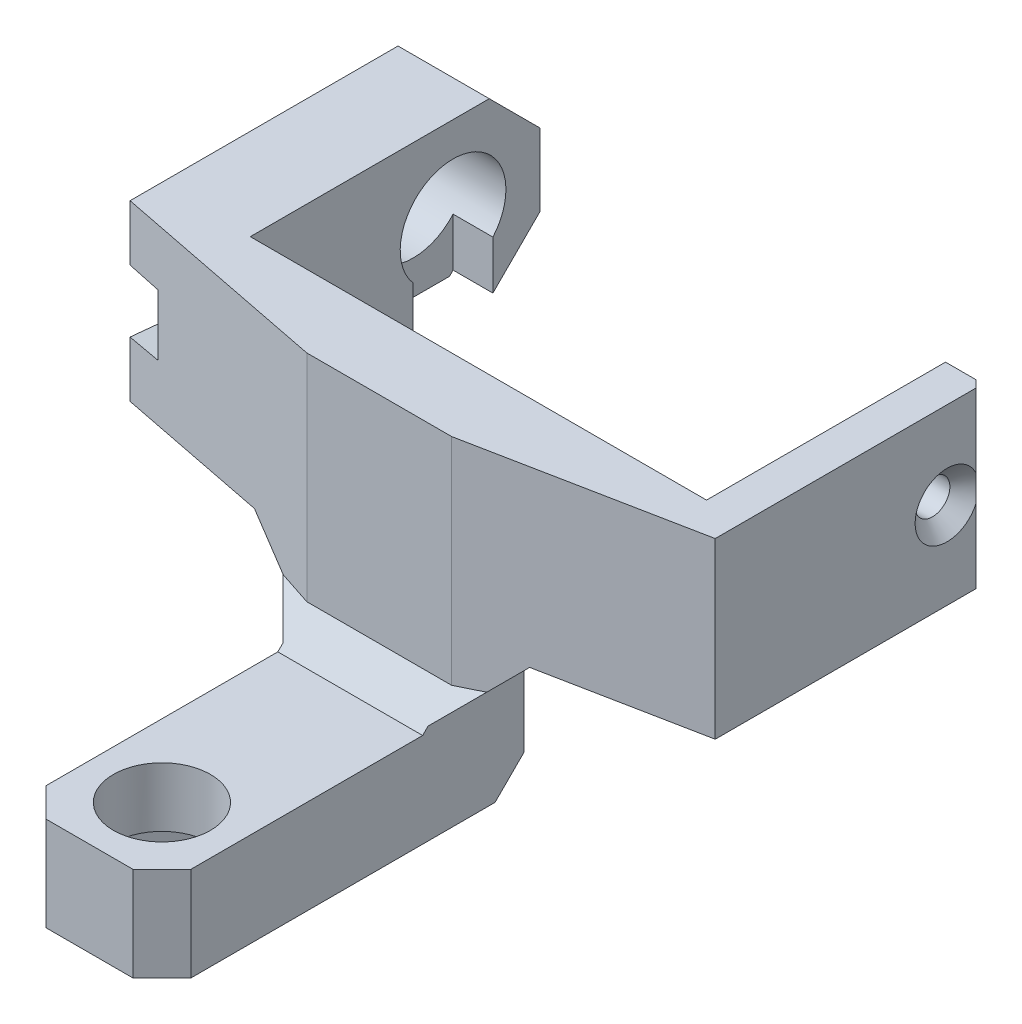
SolidWorks part; units mm, degrees
ref_plane "Front" through (0, 0, 0) normal (0, 0, 1) x (1, 0, 0)
ref_plane "Top" through (0, 0, 0) normal (0, 1, 0) x (1, 0, 0)
ref_plane "Right" through (0, 0, 0) normal (1, 0, 0) x (0, 0, -1)
sketch "Sketch1" plane through (0, 0, 0) normal (0, 0, 1) x (1, 0, 0)
  line L5 (20.2, -6) -> (-20.2, -6)
  line L6 (20.2, -6) -> (20.2, 6)
  line L7 (20.2, 6) -> (-20.2, 6)
  line L8 (-20.2, -6) -> (-20.2, 6)
  line L9 (20.2, -6) -> (-20.2, 6) construction
  line L10 (20.2, 6) -> (-20.2, -6) construction
  point P0 (0, 0)
  dimension "D1" = 40.4
  dimension "D2" = 12
extrude "Boss-Extrude1" add sketch "Sketch1" along normal blind 22 contours L7 L8 L5 L6
sketch "Sketch2" plane through (0, 6, 0) normal (0, 1, 0) x (1, 0, 0)
  line L0 (20.2, 0) -> (-20.2, 0) construction
  line L1 (-13.9, 0) -> (17.6, 0)
  line L2 (-13.9, 0) -> (-13.9, -20)
  line L3 (-13.9, -20) -> (17.6, -20)
  line L4 (17.6, 0) -> (17.6, -20)
  line L5 (-20.2, -22) -> (-20.2, 0) construction
  line L6 (20.2, -22) -> (20.2, 0) construction
  dimension "D1" = 6.3
  dimension "D2" = 31.5
  dimension "D3" = 20
  dimension "D4" = 2.6
extrude "Cut-Extrude1" cut sketch "Sketch2" against normal up to next
sketch "Sketch4" plane through (20.2, 0, 0) normal (1, 0, 0) x (0, 0, -1)
  line L0 (0, -6) -> (0, 6) construction
  circle A0 centre (-6, 0) radius 0.9
  dimension "D1" = 1.8
  dimension "D2" = 6
extrude "Cut-Extrude2" cut sketch "Sketch4" against normal up to next
ref_plane "Plane1" through (0, -36, 0) normal (0, -1, 0) x (-1, 0, 0)
sketch "Sketch14" plane through (0, 0, 22) normal (0, 0, 1) x (1, 0, 0)
  line L4 (20.2, -6) -> (20.2, 6)
  line L5 (20.2, 6) -> (-20.2, 6)
  line L6 (-20.2, 6) -> (-20.2, -6)
  line L7 (-20.2, -6) -> (20.2, -6)
  line L8 (20.2, -6) -> (20.2, 6)
  line L9 (20.2, 6) -> (-20.2, 6)
  line L10 (-20.2, 6) -> (-20.2, -6)
  line L11 (-20.2, -6) -> (20.2, -6)
  dimension "D1" = 0
chamfer "Chamfer1" distance 3.5 angle 45 4 edges at (-17.05, -6, 0) (-17.05, 6, 0) (18.9, -6, 0) (18.9, 6, 0)
hole_wizard "CSK for M2 Flat Head Machine Screw1" positions "Sketch17" profile "Sketch18" countersink size "M2" standard "ANSI Metric"
sketch "Sketch17" plane through (20.2, 0, 0) normal (1, 0, 0) x (0, 0, -1)
  point P0 (-6, 0)
sketch "Sketch18" plane through (20.2, 0, 6) normal (0, 1, 0) x (0, 0, -1)
  line L0 (0, 0) -> (0, 13.421)
  line L1 (0, 13.421) -> (1.2, 12.7)
  line L2 (1.2, 12.7) -> (1.2, 1)
  line L3 (1.2, 1) -> (2.2, 0)
  line L5 (2.2, 0) -> (0, 0)
  line L6 (-1.2, 1) -> (-2.2, 0) construction
  line L10 (0, 13.421) -> (-1.2, 12.7) construction
  line L11 (0, -6.35) -> (0, 107.95) construction
  dimension "Hole Dia." = 2.4
  dimension "Hole Depth" = 12.7
  dimension "Near C'Sink Dia." = 4.4
  dimension "Near C'Sink Angle" = 90
  dimension "Drill Angle" = 118
chamfer "Chamfer2" distance 4 angle 45 1 edges at (20.2, 0, 0)
ref_plane "Plane10" through (0, 0, 0) normal (0, -1, 0) x (-1, 0, 0)
sketch "Sketch20" plane through (17.6, 0, 0) normal (-1, 0, 0) x (0, 0, 1)
  circle A0 centre (6, 0) radius 2.5
  circle A1 centre (6, 0) radius 1.2
  dimension "D1" = 5
extrude "Boss-Extrude2" add sketch "Sketch20" along normal blind 0.5
sketch "Sketch25" plane through (0, -6, 0) normal (0, -1, 0) x (1, 0, 0)
  line L0 (0, 0) -> (0, 22) construction
  line L1 (20.2, 22) -> (-20.2, 22) construction
  line L2 (20.2, 22) -> (-20.2, 22)
  line L3 (-20.2, 22) -> (-5, 25)
  line L4 (-5, 25) -> (5, 25)
  line L5 (-13.9, 20) -> (17.6, 20) construction
  line L6 (20.2, 22) -> (5, 25)
  point P14 (0, 25)
  dimension "D1" = 5
  dimension "D2" = 5
extrude "Boss-Extrude3" add sketch "Sketch25" against normal through all
sketch "Sketch5" plane through (-20.2, 0, 0) normal (-1, 0, 0) x (0, 0, 1)
  line L0 (6, 0) -> (22.45, 0) construction
  line L1 (6.3157, 3.3351) -> (22.6196, 1.792) construction
  line L2 (6.3157, -3.3351) -> (22.6196, -1.792) construction
  line L3 (0, -2.5) -> (0, 2.5) construction
  line L4 (6.3439, 3.6338) -> (22.6479, 2.0907)
  line L5 (6.3439, -3.6338) -> (22.6479, -2.0907)
  circle A0 centre (6, 0) radius 3.35 construction
  circle A1 centre (22.45, 0) radius 1.8 construction
  arc A2 (6.3157, 3.3351) -> (6.3157, -3.3351) centre (6, 0) ccw construction
  arc A3 (22.6196, 1.792) -> (22.6196, -1.792) centre (22.45, 0) cw construction
  arc A4 (22.6479, 2.0907) -> (22.6479, -2.0907) centre (22.45, 0) cw
  arc A5 (6.3439, 3.6338) -> (6.3439, -3.6338) centre (6, 0) ccw
  point P6 (2.65, 0)
  point P7 (24.25, 0)
  point P13 (0, 0)
  dimension "D1" = 6.7
  dimension "D2" = 3.6
  dimension "D4" = 0.3
  dimension "D3" = 21.6
  dimension "D5" = 6
extrude "Cut-Extrude3" cut sketch "Sketch5" against normal blind 2.4
sketch "Sketch23" plane through (-17.8, 0, 0) normal (-1, 0, 0) x (0, 0, 1)
  circle A0 centre (6, 0) radius 3.65
  arc A1 (6.3439, 3.6338) -> (6.3439, -3.6338) centre (6, 0) ccw construction
extrude "Cut-Extrude4" cut sketch "Sketch23" against normal blind 22.4
sketch "Sketch24" plane through (0, 0, 0) normal (0, -1, 0) x (-1, 0, 0)
  line L0 (13.9, -2.35) -> (13.9, -9.65) construction
  line L1 (16.65, -8.75) -> (11.15, -8.75)
  line L2 (16.65, -8.75) -> (16.65, -3.25)
  line L3 (16.65, -3.25) -> (11.15, -3.25)
  line L4 (11.15, -8.75) -> (11.15, -3.25)
  line L5 (16.65, -8.75) -> (11.15, -3.25) construction
  line L6 (16.65, -3.25) -> (11.15, -8.75) construction
  point P0 (13.9, -6)
  dimension "D1" = 5.5
extrude "Cut-Extrude5" cut sketch "Sketch24" along normal blind 22.4
sketch "Sketch26" plane through (0, -6, 0) normal (0, 1, 0) x (1, 0, 0)
  line L0 (-13.9, -20) -> (17.6, -20) construction
  line L1 (-5, -25) -> (5, -25)
  line L2 (-5, -25) -> (-5, -20)
  line L3 (-5, -20) -> (5, -20)
  line L4 (5, -25) -> (5, -20)
extrude "Boss-Extrude4" add sketch "Sketch26" against normal blind 11.375
sketch "Sketch27" plane through (0, -17.375, 0) normal (0, -1, 0) x (-1, 0, 0)
  line L0 (-5, -25) -> (-5, -20) construction
  line L1 (5, -20) -> (-5, -20)
  line L2 (5, -20) -> (5, -45)
  line L3 (5, -45) -> (-5, -45)
  line L4 (-5, -20) -> (-5, -45)
  line L5 (5, -20) -> (5, -25) construction
  line L6 (-5, -20) -> (5, -20) construction
  dimension "D1" = 25
extrude "Boss-Extrude5" add sketch "Sketch27" against normal blind 6.5
sketch "Sketch28" plane through (0, -17.375, 0) normal (0, -1, 0) x (-1, 0, 0)
  line L0 (0, -21.75) -> (0, -43.35) construction
  line L1 (-1.792, -23.3804) -> (-3.3351, -39.6843)
  line L2 (1.792, -23.3804) -> (3.3351, -39.6843)
  line L4 (-5, -45) -> (5, -45) construction
  arc A0 (-3.3351, -39.6843) -> (3.3351, -39.6843) centre (0, -40) ccw
  arc A1 (1.792, -23.3804) -> (-1.792, -23.3804) centre (0, -23.55) ccw
  dimension "D1" = 6.7
  dimension "D2" = 3.6
  dimension "D3" = 21.6
  dimension "D4" = 5
extrude "Cut-Extrude6" cut sketch "Sketch28" against normal blind 2.4
sketch "Sketch29" plane through (0, -14.975, 0) normal (0, -1, 0) x (-1, 0, 0)
  circle A0 centre (0, -40) radius 3.35
  arc A1 (-3.3351, -39.6843) -> (3.3351, -39.6843) centre (0, -40) ccw construction
extrude "Cut-Extrude7" cut sketch "Sketch29" against normal through all
chamfer "Chamfer3" distance 2 angle 45 3 edges at (5, -14.125, 45) (-5, -14.125, 45) (0, -17.375, 20)
chamfer "Chamfer5" distance 2 angle 45 1 edges at (0, -10.875, 25)
chamfer "Chamfer6" distance 4.5 angle 45 2 edges at (5, -6, 22.5) (-5, -6, 22.5)
ref_plane "Plane11" through (0, 3.65, 0) normal (0, -1, 0) x (-1, 0, 0)
ref_plane "Plane12" through (0, -3.65, 0) normal (0, 1, 0) x (1, 0, 0)
ref_plane "Plane13" through (0, 0, 0) normal (0, 1, 0) x (1, 0, 0)
